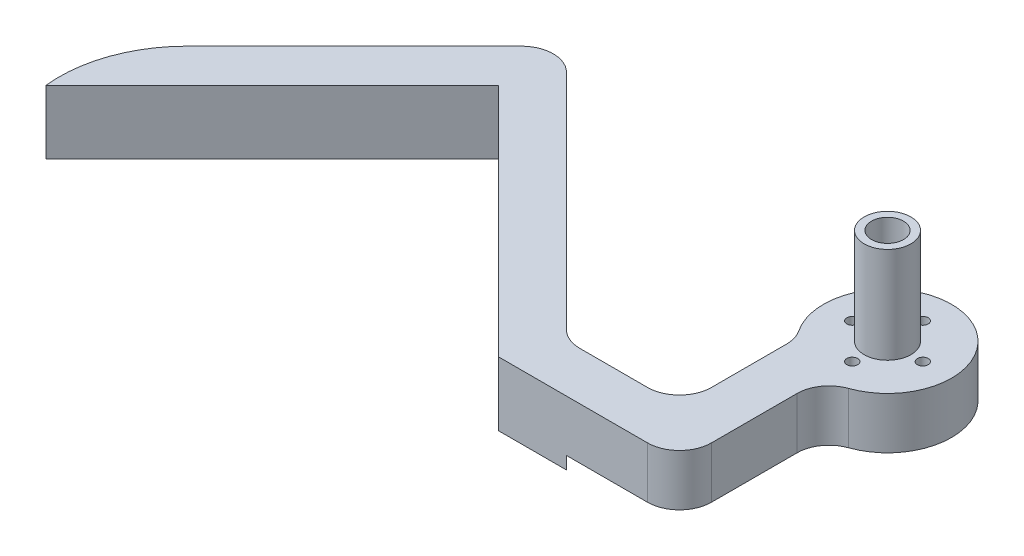
SolidWorks part; units mm, degrees
ref_plane "Front Plane" through (0, 0, 0) normal (0, 0, 1) x (1, 0, 0)
ref_plane "Top Plane" through (0, 0, 0) normal (0, 1, 0) x (1, 0, 0)
ref_plane "Right Plane" through (0, 0, 0) normal (1, 0, 0) x (0, 0, -1)
sketch "Sketch1" plane through (0, 0, 0) normal (0, 1, 0) x (1, 0, 0)
  circle A3 centre (0, -38.254) radius 38.254 construction
  circle A4 centre (0, -40.254) radius 40.254 construction
  circle A5 centre (0, -45.254) radius 45.254 construction
  dimension "D1" = 90.508
  dimension "D2" = 80.508
  dimension "D3" = 76.508
sketch "Sketch3" plane through (0, 0, 0) normal (0, 1, 0) x (1, 0, 0)
  line L8 (58.3717, -39.6268) -> (0, 18.7448)
  line L9 (0, 18.7448) -> (-58.3717, -39.6268)
  line L10 (-58.3717, -39.6268) -> (58.3717, -39.6268) construction
  line L17 (65.1069, -32.8917) -> (60.1326, -27.9174)
  line L18 (0, 32.2152) -> (-65.1069, -32.8917)
  line L19 (-65.1069, -32.8917) -> (-58.3717, -39.6268)
  line L20 (65.1069, -32.8917) -> (58.3717, -39.6268)
  line L23 (82.55, -18.3924) -> (82.55, -27.9174)
  line L26 (65.1069, -32.8917) -> (0, 32.2152) construction
  line L27 (0, 32.2152) -> (-65.1069, -32.8917) construction
  line L28 (50.6076, -18.3924) -> (73.025, -18.3924)
  line L29 (82.55, -27.9174) -> (60.1326, -27.9174)
  line L30 (50.6076, -18.3924) -> (0, 32.2152)
  line L31 (82.55, -18.3924) -> (82.55, 13.3576)
  line L32 (82.55, 13.3576) -> (73.025, 13.3576)
  line L33 (73.025, 13.3576) -> (73.025, -18.3924)
  circle A3 centre (0, -45.254) radius 45.254 construction
  dimension "D1" = 45
  dimension "D2" = 45
  dimension "D3" = 82.55
  dimension "D5" = 9.525
  dimension "D7" = 82.55
  dimension "D6" = 9.525
  dimension "D8" = 52.9844
  dimension "D9" = 31.75
  dimension "D4" = 9.525
extrude "Boss-Extrude1" add sketch "Sketch3" along normal blind 19.05
sketch "Sketch11" plane through (0, 0, 0) normal (0, 1, 0) x (1, 0, 0)
  circle A0 centre (82.55, 13.3576) radius 12.7
  dimension "D1" = 25.4
extrude "Boss-Extrude2" add sketch "Sketch11" along normal blind 19.05
sketch "Sketch14" plane through (0, 0, 0) normal (0, -1, 0) x (1, 0, 0)
  circle A0 centre (89.55, -13.3576) radius 1.077
  circle A2 centre (82.55, -20.3576) radius 1.077
  circle A3 centre (75.55, -13.3576) radius 1.077
  circle A4 centre (82.55, -6.3576) radius 1.077
  circle A5 centre (82.55, -13.3576) radius 12.7 construction
  point P17 (82.55, -13.3576)
  dimension "D2" = 2.154
  dimension "D1" = 7
  dimension "D3" = 4
extrude "Cut-Extrude4" cut sketch "Sketch14" against normal through all
sketch "Sketch16" plane through (0, 0, 0) normal (0, -1, 0) x (1, 0, 0)
  line L2 (60.1326, 27.9174) -> (50.6076, 18.3924)
  line L7 (-65.1069, 32.8917) -> (0, -32.2152)
  line L8 (65.1069, 32.8917) -> (58.3717, 39.6268)
  line L9 (58.3717, 39.6268) -> (0, -18.7448)
  line L10 (0, -18.7448) -> (-58.3717, 39.6268)
  line L20 (-58.3717, 39.6268) -> (-65.1069, 32.8917)
  line L24 (50.6076, 18.3924) -> (73.025, 18.3924)
  line L30 (60.1326, 27.9174) -> (65.1069, 32.8917)
  line L35 (50.6076, 18.3924) -> (73.025, 18.3924)
  line L37 (82.55, 27.9174) -> (60.1326, 27.9174)
  line L38 (82.55, 27.9174) -> (60.1326, 27.9174)
  line L40 (0, -32.2152) -> (50.6076, 18.3924)
  line L47 (82.55, -0.6576) -> (82.55, 27.9174)
  line L48 (82.55, -0.6576) -> (82.55, 27.9174)
  line L49 (73.025, 18.3924) -> (73.025, -4.9573)
  line L50 (73.025, 18.3924) -> (73.025, -4.9573)
  arc A1 (73.025, -4.9573) -> (82.55, -0.6576) centre (82.55, -13.3576) ccw
  arc A6 (73.025, -4.9573) -> (82.55, -0.6576) centre (82.55, -13.3576) ccw
  dimension "D1" = 0
extrude "Cut-Extrude7" cut sketch "Sketch16" against normal blind 8.842
sketch "Sketch17" plane through (0, 19.05, 0) normal (0, 1, 0) x (1, 0, 0)
  line L0 (-65.1069, -32.8917) -> (-51.6365, -19.4213)
  line L1 (0, 32.2152) -> (-65.1069, -32.8917) construction
  line L2 (-51.6365, -19.4213) -> (-44.9013, -26.1565)
  line L3 (-58.3717, -39.6268) -> (0, 18.7448) construction
  line L4 (-44.9013, -26.1565) -> (-58.3717, -39.6268)
  line L5 (-58.3717, -39.6268) -> (-65.1069, -32.8917)
  dimension "D1" = 19.05
extrude "Cut-Extrude8" cut sketch "Sketch17" against normal through all
fillet "Fillet10" radius 25.4 1 edges at (-51.6365, 9.525, 19.4213)
sketch "Sketch18" plane through (0, 19.05, 0) normal (0, 1, 0) x (1, 0, 0)
  circle A0 centre (82.55, 13.3576) radius 3.175
  dimension "D1" = 6.35
extrude "Cut-Extrude9" cut sketch "Sketch18" against normal through all
sketch "Sketch19" plane through (0, 19.05, 0) normal (0, 1, 0) x (1, 0, 0)
  circle A0 centre (82.55, 13.3576) radius 3.175
  circle A1 centre (82.55, 13.3576) radius 4.6355
  dimension "D1" = 9.271
extrude "Boss-Extrude3" add sketch "Sketch19" along normal offset from surface (19.05 mm away) 38.1 up to face at (6.433, 0, 8.7144)
sketch "Sketch20" plane through (0, 0, 0) normal (0, -1, 0) x (1, 0, 0)
  line L5 (0, -18.7448) -> (-44.9013, 26.1565)
  line L6 (-37.6161, 5.4008) -> (0, -32.2152)
  line L7 (0, -32.2152) -> (65.1069, 32.8917)
  line L8 (65.1069, 32.8917) -> (58.3717, 39.6268)
  line L9 (58.3717, 39.6268) -> (0, -18.7448)
  line L10 (0, -18.7448) -> (-44.9013, 26.1565)
  line L11 (-37.6161, 5.4008) -> (0, -32.2152)
  line L12 (0, -32.2152) -> (65.1069, 32.8917)
  line L13 (65.1069, 32.8917) -> (58.3717, 39.6268)
  line L14 (58.3717, 39.6268) -> (0, -18.7448)
  arc A1 (-44.9013, 26.1565) -> (-37.6161, 5.4008) centre (-19.6555, 23.3614) ccw
  arc A3 (-44.9013, 26.1565) -> (-37.6161, 5.4008) centre (-19.6555, 23.3614) ccw
  dimension "D1" = 0
extrude "Cut-Extrude10" cut sketch "Sketch20" against normal blind 6.35
sketch "Sketch21" plane through (0, 19.05, 0) normal (0, 1, 0) x (1, 0, 0)
  line L0 (60.1326, -27.9174) -> (46.6623, -27.9174)
  line L1 (0, 18.7448) -> (58.3717, -39.6268) construction
  line L2 (46.6623, -27.9174) -> (58.3717, -39.6268)
  line L3 (58.3717, -39.6268) -> (65.1069, -32.8917)
  line L4 (65.1069, -32.8917) -> (60.1326, -27.9174)
extrude "Cut-Extrude11" cut sketch "Sketch21" against normal through all
fillet "Fillet11" radius 6.35 6 edges at (82.55, 13.946, 27.9174) (82.55, 13.946, -0.6576) (73.025, 13.946, -4.9573) (73.025, 13.946, 18.3924) (50.6076, 13.946, 18.3924) (0, 12.7, -32.2152)
equation "\"tightTol\"= 0.005in"
equation "\"normTol\"= 0.01in"
equation "\"looseTol\"= 0.02in"
equation "\"D1@Sketch1\"=\"looseTol\"+9cm"
equation "\"D2@Sketch1\"=8cm+\"looseTol\""
equation "\"D3@Sketch1\"=7.6cm+\"looseTol\""
equation "\"D2\"= 0.875 - 10.7mm"
equation "\"D1\"= 10.7mm"
equation "\"D1@Boss-Extrude1\"=40mm"
equation "\"D2@Sketch14\"= 1.9mm + \"normTol\""
equation "\"D1@Sketch14\"= 7mm"
equation "\"D19@Boss-Extrude2\"=0.250000-1.5*\"normTol\""
equation "\"D1@Boss-Extrude2\"= 0.75"
equation "\"D1@Cut-Extrude7\" = 15.7mm - 0.25 - \"looseTol\""
equation "\"D1@Sketch19\"=0.375000in-\"normTol\""
equation "\"D8@Sketch3\"=4.95-2.864"
